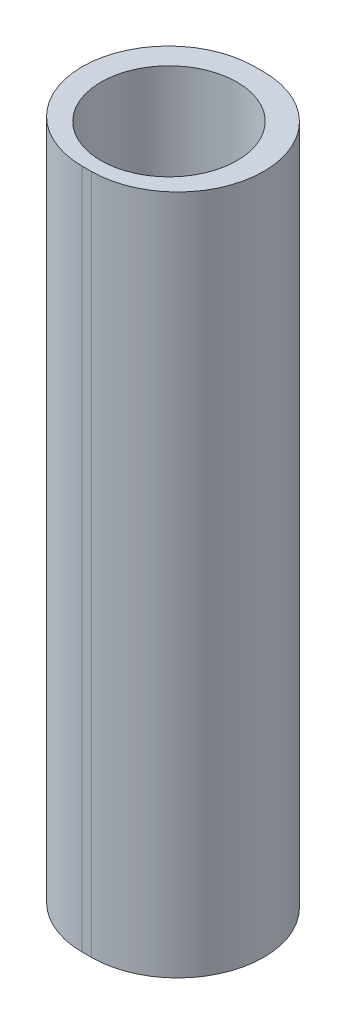
SolidWorks part; units mm, degrees
ref_plane "Front Plane" through (0, 0, 0) normal (0, 0, 1) x (1, 0, 0)
ref_plane "Top Plane" through (0, 0, 0) normal (0, 1, 0) x (1, 0, 0)
ref_plane "Right Plane" through (0, 0, 0) normal (1, 0, 0) x (0, 0, -1)
sketch "Sketch1" plane through (0, 0, 0) normal (1, 0, 0) x (0, 0, -1)
  line L1 (0, 0) -> (3.8, 0)
  line L2 (0, 0) -> (0, 15)
  line L3 (0, 15) -> (3.8, 15)
  line L4 (3.8, 0) -> (3.8, 15)
  dimension "D1" = 15
  dimension "D2" = 3.8
extrude "Boss-Extrude1" add sketch "Sketch1" along normal blind 2
fillet "Fillet1" 2 edges at (2, 7.5, 0) (2, 7.5, -3.8) type full round first side face at (1, 7.5, 0) second side face at (1, 7.5, -3.8) middle face at (2, 7.5, -1.9)
mirror "Mirror1" about plane through (0, 0, 0) normal (-1, 0, 0) of "Fillet1", "Boss-Extrude1"
sketch "Sketch3" plane through (0, 0, 0) normal (0, -1, 0) x (1, 0, 0)
  circle A0 centre (0, -1.8113) radius 1.5
  dimension "D1" = 3
extrude "Cut-Extrude1" cut sketch "Sketch3" against normal blind 15 contours A0
